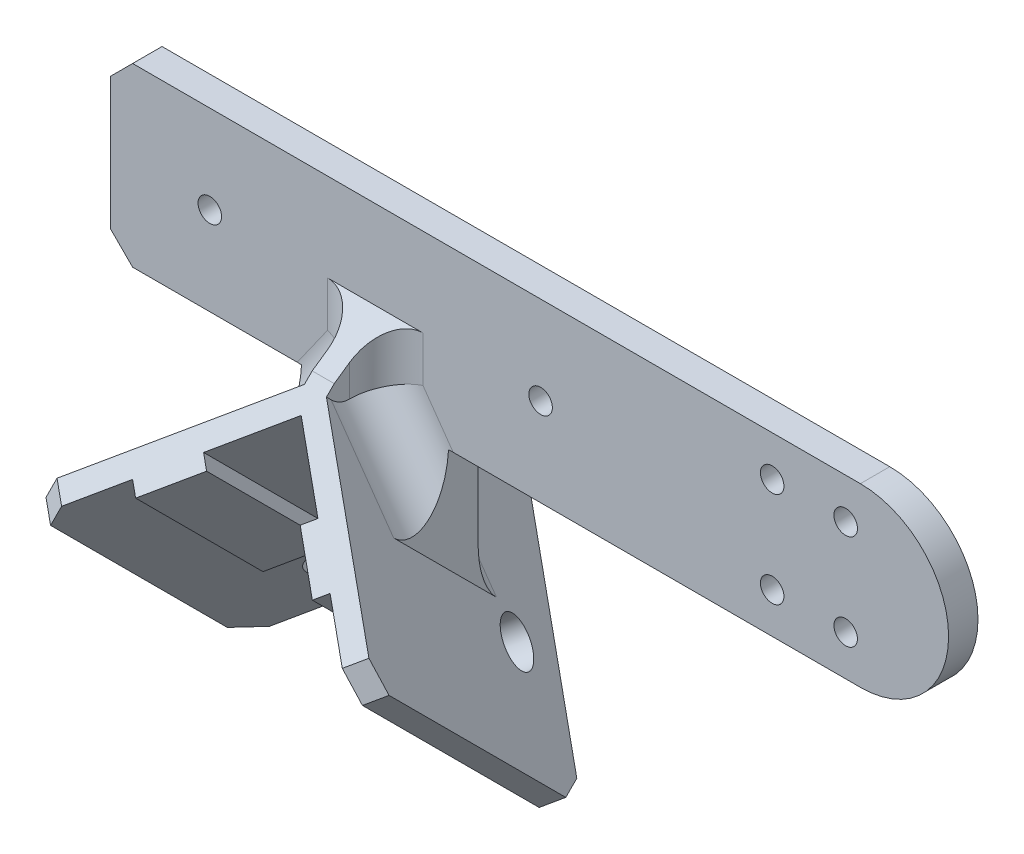
SolidWorks part; units mm, degrees
ref_plane "Alzado" through (0, 0, 0) normal (0, 0, 1) x (1, 0, 0)
ref_plane "Planta" through (0, 0, 0) normal (0, 1, 0) x (1, 0, 0)
ref_plane "Vista lateral" through (0, 0, 0) normal (1, 0, 0) x (0, 0, -1)
sketch "Croquis1" plane through (0, 0, 0) normal (0, 0, 1) x (1, 0, 0)
  line L0 (0, 0) -> (0, 18835.1574) construction
  line L1 (0, 0) -> (-18835.1574, 0) construction
  line L2 (10, -12) -> (36, -12)
  line L3 (-36, -12) -> (36, -12) construction
  line L4 (-36, -12) -> (-36, 12)
  line L5 (-36, 12) -> (36, 12)
  line L6 (36, -12) -> (36, 12)
  line L7 (-36, -12) -> (36, 12) construction
  line L8 (-36, 12) -> (36, -12) construction
  line L9 (-17.5, 6) -> (17.5, 6) construction
  line L10 (-17.5, 6) -> (-17.5, -6) construction
  line L11 (-17.5, -6) -> (17.5, -6) construction
  line L12 (17.5, 6) -> (17.5, -6) construction
  line L13 (-17.5, 6) -> (17.5, -6) construction
  line L14 (-17.5, -6) -> (17.5, 6) construction
  line L15 (-10, -32) -> (10, -32)
  line L16 (-10, -32) -> (-10, -12)
  line L17 (-10, -12) -> (10, -12) construction
  line L18 (10, -32) -> (10, -12)
  line L19 (-10, -32) -> (10, -12) construction
  line L20 (-10, -12) -> (10, -32) construction
  line L21 (-36, -12) -> (-10, -12)
  circle A0 centre (-22.5, 0) radius 1.6
  circle A1 centre (22.5, 0) radius 1.6
  point P7 (0, 0)
  point P12 (0, -22)
  point P16 (0, 0)
  dimension "D1" = 3.2
  dimension "D2" = 45
  dimension "D3" = 24
  dimension "D4" = 13.5
  dimension "D5" = 35
  dimension "D6" = 12
  dimension "D7" = 20
  dimension "D8" = 20
extrude "Saliente-Extruir1" add sketch "Croquis1" along normal blind 4
sketch "Croquis3" plane through (0, 0, 0) normal (0, 0, -1) x (-1, 0, 0)
  line L0 (0, 0) -> (-50000, 0) construction
  line L1 (-66, 12) -> (-36, 12)
  line L2 (-66, -12) -> (-36, -12)
  line L3 (-36, -12) -> (-36, 12)
  line L4 (-36, -12) -> (-36, 12) construction
  arc A0 (-66, 12) -> (-66, -12) centre (-66, 0) ccw
  circle A1 centre (-54, 6.5) radius 1.6
  circle A2 centre (-64, 6.5) radius 1.6
  circle A3 centre (-54, -6.5) radius 1.6
  circle A4 centre (-64, -6.5) radius 1.6
  dimension "D1" = 30
  dimension "D2" = 3.2
  dimension "D5" = 28
  dimension "D3" = 13
  dimension "D4" = 18
extrude "Saliente-Extruir3" add sketch "Croquis3" against normal blind 4
ref_plane "Plano1" through (0, -4, -4) normal (0, -0.7071, -0.7071) x (1, 0, 0)
sketch "Croquis5" plane through (0, -4.201, -3.799) normal (0, 0.7071, 0.7071) x (1, 0, 0)
  line L0 (0, 0) -> (0, 50000) construction
  line L2 (-21.2132, -36.4853) -> (0, -15.2721) construction
  line L5 (-13.435, -28.7071) -> (-21.2132, -36.4853)
  line L11 (-10, -11.0294) -> (49990, -11.0294) construction
  line L12 (0, -11.0294) -> (23.3345, -34.364)
  line L13 (23.3345, -34.364) -> (21.2132, -36.4853)
  line L14 (21.2132, -36.4853) -> (0, -15.2721) construction
  line L38 (10.6066, -25.8787) -> (35365.9457, 35329.4604) construction
  line L39 (0, -15.2721) -> (-7.7782, -23.0503)
  line L40 (7.7782, -23.0503) -> (6.364, -24.4645)
  line L41 (6.364, -24.4645) -> (12.0208, -30.1213)
  line L42 (12.0208, -30.1213) -> (13.435, -28.7071)
  line L43 (0, -15.2721) -> (7.7782, -23.0503)
  line L44 (13.435, -28.7071) -> (21.2132, -36.4853)
  line L45 (-12.0208, -30.1213) -> (-13.435, -28.7071)
  line L46 (-6.364, -24.4645) -> (-12.0208, -30.1213)
  line L47 (-7.7782, -23.0503) -> (-6.364, -24.4645)
  line L48 (-23.3345, -34.364) -> (-21.2132, -36.4853)
  line L49 (0, -11.0294) -> (-23.3345, -34.364)
  point P10 (11.3222, -29.4227)
  point P11 (13.1978, -28.4698)
  point P13 (10.6066, -25.8787)
  point P19 (9.1924, -27.2929)
  dimension "D1" = 45
  dimension "D2" = 30
  dimension "D3" = 3
  dimension "D4" = 2
  dimension "D5" = 8
extrude "Saliente-Extruir4" add sketch "Croquis5" against normal blind 30 and the other way blind 10
sketch "Croquis13" plane through (-9.1924, -6.5, 6.5) normal (-0.7071, -0.5, 0.5) x (0.4082, 0.2887, 0.866)
  line L0 (-10.0201, -38.9287) -> (40814.8089, 28828.5848) construction
  line L1 (-16.412, -38.5494) -> (-11.7932, -45.0814) construction
  circle A0 centre (-7.5706, -37.1966) radius 3.1
  point P4 (-14.1026, -41.8154)
  dimension "D1" = 6.2
  dimension "D2" = 8
extrude "Cortar-Extruir8" cut sketch "Croquis13" against normal up to next
sketch "Croquis14" plane through (-9.1924, -6.5, 6.5) normal (-0.7071, -0.5, 0.5) x (0.4082, 0.2887, 0.866)
  line L0 (-13.5543, -36.5287) -> (-8.9355, -43.0607)
  line L1 (-5.1962, -30.6186) -> (-16.412, -38.5494) construction
  line L2 (20.8667, -21.9874) -> (-11.7932, -45.0814) construction
  line L3 (-8.9355, -43.0607) -> (-1.587, -37.8645)
  line L4 (20.8667, -21.9874) -> (-11.7932, -45.0814) construction
  line L5 (-1.587, -37.8645) -> (-6.2058, -31.3325)
  line L6 (-4.0415, -29.8021) -> (-16.412, -38.5494) construction
  line L7 (-6.2058, -31.3325) -> (-13.5543, -36.5287)
  line L8 (-9.88, -33.9306) -> (-5.2612, -40.4626) construction
  point P16 (-7.5706, -37.1966)
  dimension "D1" = 9
extrude "Cortar-Extruir9" cut sketch "Croquis14" against normal up to surface (2 mm away) up to face at (17.3241, -34.3211, 12.1789)
sketch "Croquis15" plane through (6.1283, -4.3333, 13) normal (0.7071, -0.5, 0.5) x (0.6667, 0.2357, -0.7071)
  line L0 (-8.4296, -38.5546) -> (40817.8926, 28826.8468) construction
  line L2 (-19.8325, -8.9052) -> (16646.8342, -47149.3573) construction
  line L3 (-23.6037, -10.2386) -> (-16.0613, -7.5719) construction
  line L4 (-10.2704, -47.9509) -> (-2.7279, -45.2843) construction
  circle A0 centre (-9.1658, -39.0751) radius 3.1
  point P8 (-19.8325, -8.9052)
  point P11 (-6.4992, -46.6176)
  point P12 (-12.2495, -37.3371)
  point P13 (0, 0)
  dimension "D1" = 6.2
  dimension "D2" = 8
extrude "Cortar-Extruir10" cut sketch "Croquis15" against normal up to next
sketch "Croquis17" plane through (6.1283, -4.3333, 13) normal (0.7071, -0.5, 0.5) x (0.6667, 0.2357, -0.7071)
  line L0 (-11.4371, -44.6511) -> (-3.8946, -41.9844)
  line L3 (-3.8946, -41.9844) -> (-6.8946, -33.4992)
  line L5 (-6.8946, -33.4992) -> (-14.4371, -36.1658)
  line L7 (-14.4371, -36.1658) -> (-11.4371, -44.6511)
  line L8 (-12.9371, -40.4085) -> (-5.3946, -37.7418) construction
  line L10 (-7.7782, -31) -> (-2.7279, -45.2843) construction
  line L11 (-23.6037, -10.2386) -> (-10.2704, -47.9509) construction
  line L12 (-23.6037, -10.2386) -> (-10.2704, -47.9509) construction
  point P2 (-13.1428, -24.272)
  point P3 (-9.1658, -39.0751)
  point P5 (-14.4351, -36.1713)
  point P11 (-9.1658, -39.0751)
  point P16 (-11.9894, -40.0734)
  dimension "D1" = 9
extrude "Cortar-Extruir11" cut sketch "Croquis17" against normal up to surface (2 mm away) up to face at (-17.3241, -34.3211, 12.1789)
sketch "Croquis18" plane through (0, 3.0711, 3.0711) normal (0, 0.7071, 0.7071) x (1, 0, 0)
  line L0 (-7.0711, -25.4558) -> (-6.364, -24.7487)
  line L1 (-12.0208, -30.4056) -> (-6.364, -24.7487) construction
  line L2 (-7.0711, -25.4558) -> (-6.364, -24.7487) construction
  line L3 (-6.364, -24.7487) -> (-7.7782, -23.3345)
  line L4 (-7.7782, -23.3345) -> (0, -15.5563)
  line L5 (0, -15.5563) -> (7.7782, -23.3345) construction
  line L6 (-7.7782, -23.3345) -> (0, -15.5563) construction
  line L7 (0, -15.5563) -> (7.7782, -23.3345)
  line L8 (7.7782, -23.3345) -> (6.364, -24.7487)
  line L9 (6.364, -24.7487) -> (7.0711, -25.4558)
  line L10 (7.0711, -25.4558) -> (-7.0711, -25.4558)
extrude "Cortar-Extruir12" cut sketch "Croquis18" against normal through all
sketch "Croquis19" plane through (0, 0, 0) normal (1, 0, 0) x (0, 0, -1)
  line L0 (-11.0711, -4.9289) -> (-12.6368, -6.4947)
  line L1 (-27.5711, -21.4289) -> (-11.0711, -4.9289) construction
  line L2 (-12.6368, -6.4947) -> (-4, -15.6422)
  line L3 (-4, -26.1421) -> (-4, -12) construction
  line L4 (-4, -15.6422) -> (-4, 0)
  line L5 (-4, 12) -> (-4, -12) construction
  line L6 (-4, 0) -> (-11.0711, -4.9289)
extrude "Saliente-Extruir5" add sketch "Croquis19" along normal mid plane 3
fillet "Redondeo1" radius 5 4 edges at (1.5, -7.0607, 4) (5.75, -20.1317, 4) (-5.75, -20.1317, 4) (-1.5, -7.0607, 4)
chamfer "Chaflán1" distance 3 angle 45 8 edges at (22.2739, -22.1789, 28.3211) (22.2739, -50.4632, 0.0368) (-22.2739, -22.1789, 28.3211) (-22.2739, -50.4632, 0.0368) (-36, -12, 2) (-36, 12, 2) (9.1924, -35.8744, 3.1256) (-9.1924, -35.8744, 3.1256)
fillet "Redondeo2" radius 5 2 edges at (-5, -23.0711, 0) (5, -23.0711, 0)
